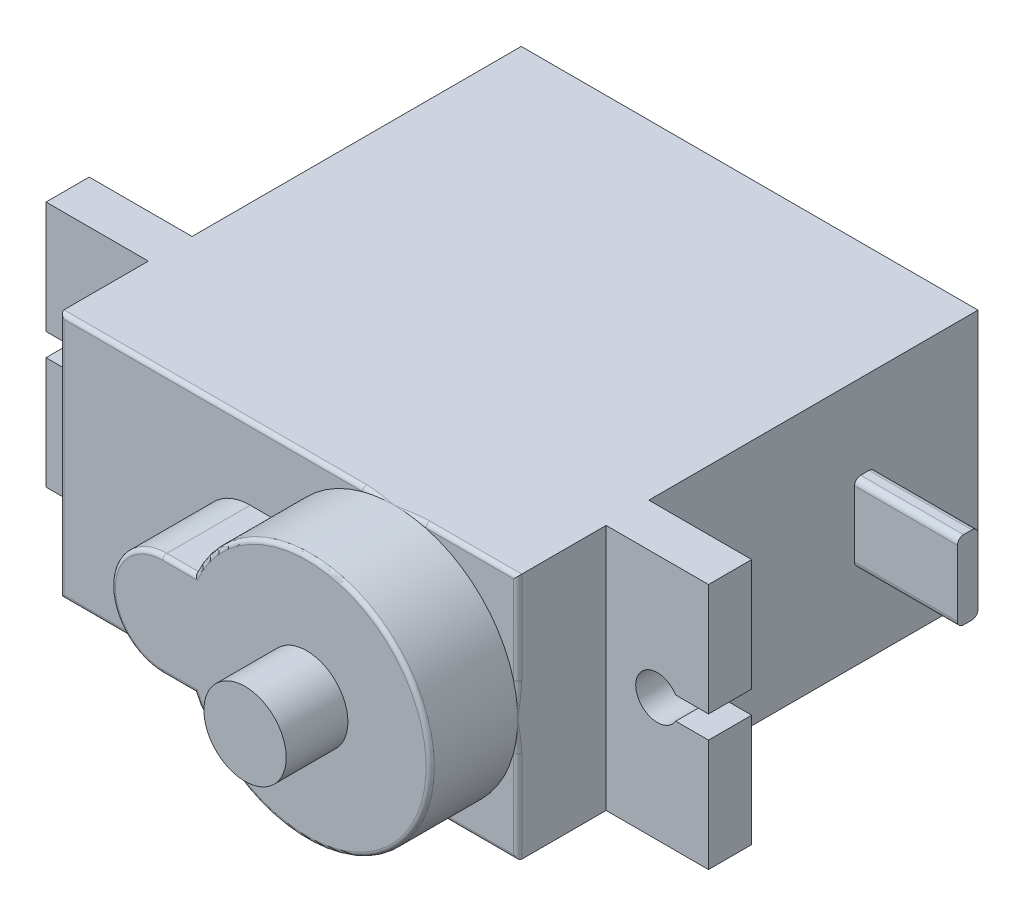
SolidWorks part; units mm, degrees
ref_plane "Ebene vorne" through (0, 0, 0) normal (0, 0, 1) x (1, 0, 0)
ref_plane "Ebene oben" through (0, 0, 0) normal (0, 1, 0) x (1, 0, 0)
ref_plane "Ebene rechts" through (0, 0, 0) normal (1, 0, 0) x (0, 0, -1)
sketch "BasisSkizze" plane through (0, 0, 0) normal (0, 0, 1) x (1, 0, 0)
  line L1 (-16.1, 6) -> (16.1, 6)
  line L2 (-16.1, 6) -> (-16.1, -6)
  line L3 (-16.1, -6) -> (16.1, -6)
  line L4 (16.1, 6) -> (16.1, -6)
  line L5 (-16.1, 6) -> (16.1, -6) construction
  line L6 (-16.1, -6) -> (16.1, 6) construction
  point P0 (0, 0)
  dimension "D1" = 32.2
  dimension "D2" = 12
extrude "Basis" add sketch "BasisSkizze" along normal mid plane 2.1
sketch "Skizze2" plane through (0, 0, 1.05) normal (0, 0, 1) x (1, 0, 0)
  line L0 (-16.1, -6) -> (16.1, -6) construction
  line L1 (-11.125, 6) -> (11.125, 6)
  line L2 (-11.125, 6) -> (-11.125, -6)
  line L3 (-11.125, -6) -> (11.125, -6)
  line L4 (11.125, 6) -> (11.125, -6)
  line L5 (-11.125, 6) -> (11.125, -6) construction
  line L6 (-11.125, -6) -> (11.125, 6) construction
  point P0 (0, 0)
  dimension "D1" = 22.25
extrude "Body oben" add sketch "Skizze2" along normal blind 4.3
sketch "Getriebe" plane through (0, 0, 5.35) normal (0, 0, 1) x (1, 0, 0)
  line L0 (-11.125, 0) -> (11.125, 0) construction
  line L1 (-11.125, 6) -> (-11.125, -6) construction
  line L2 (11.125, -6) -> (11.125, 6) construction
  line L3 (-1.875, 2.5) -> (-0.3294, 2.5)
  line L4 (-1.875, -2.5) -> (-0.3294, -2.5)
  circle A0 centre (5.125, 0) radius 6
  circle A1 centre (-1.875, 0) radius 2.5 construction
  arc A2 (-1.875, 2.5) -> (-1.875, -2.5) centre (-1.875, 0) ccw
  dimension "D1" = 6
  dimension "D2" = 12
  dimension "D3" = 5
  dimension "D4" = 7
extrude "Getriebeaufsatz" add sketch "Getriebe" along normal blind 4.25 contours L3 A2 L4 A0 | A0 region at (-2.3129, 0, 5.35) region at (5.125, 0, 5.35)
fillet "Verrundung1" radius 0.2 7 edges at (8.125, 6, 5.35) (11.125, 3, 5.35) (8.125, -6, 5.35) (-3, 6, 5.35) (11.125, -3, 5.35) (-3, -6, 5.35) (-11.125, 0, 5.35)
fillet "Verrundung2" radius 0.2 4 edges at (-1.1022, 2.5, 9.6) (11.125, 0, 9.6) (-1.1022, -2.5, 9.6) (-4.375, 0, 9.6)
sketch "Skizze5" plane through (0, 0, 9.6) normal (0, 0, 1) x (1, 0, 0)
  line L0 (5.125, 5.8) -> (5.125, -5.8) construction
  line L1 (-4.175, 0) -> (10.925, 0) construction
  arc A0 (-0.1995, -2.3) -> (-0.1995, 2.3) centre (5.125, 0) ccw construction
  arc A1 (-1.875, 2.3) -> (-1.875, -2.3) centre (-1.875, 0) ccw construction
  circle A2 centre (5.125, 0) radius 2
  dimension "D1" = 4
extrude "Stutzen" add sketch "Skizze5" along normal blind 3
sketch "Skizze6" plane through (0, 0, -1.05) normal (0, 0, -1) x (-1, 0, 0)
  line L0 (16.1, -6) -> (-16.1, -6) construction
  line L1 (-11.1, 6) -> (11.1, 6)
  line L2 (-11.1, 6) -> (-11.1, -6)
  line L3 (-11.1, -6) -> (11.1, -6)
  line L4 (11.1, 6) -> (11.1, -6)
  line L5 (-11.1, 6) -> (11.1, -6) construction
  line L6 (-11.1, -6) -> (11.1, 6) construction
  point P0 (0, 0)
  dimension "D1" = 22.2
extrude "Body unten" add sketch "Skizze6" along normal blind 16
sketch "Skizze7" plane through (11.1, 0, 0) normal (1, 0, 0) x (0, 0, -1)
  line L0 (17.05, 0) -> (-12.3825, 0) construction
  line L1 (11.05, -1.9) -> (12.05, -1.9)
  line L2 (11.05, -1.9) -> (11.05, 1.9)
  line L3 (11.05, 1.9) -> (12.05, 1.9)
  line L4 (12.05, -1.9) -> (12.05, 1.9)
  line L5 (11.05, -1.9) -> (12.05, 1.9) construction
  line L6 (11.05, 1.9) -> (12.05, -1.9) construction
  line L7 (17.05, 6) -> (17.05, -6) construction
  point P0 (11.55, 0)
  dimension "D1" = 1
  dimension "D2" = 3.8
  dimension "D3" = 5.5
extrude "Aufsatz-Linear austragen6" add sketch "Skizze7" along normal blind 5
fillet "Verrundung3" radius 0.3 4 edges at (13.6, 1.9, -11.05) (13.6, 1.9, -12.05) (13.6, -1.9, -12.05) (13.6, -1.9, -11.05)
sketch "Schraubenhalterungsskizze" plane through (0, 0, 1.05) normal (0, 0, 1) x (1, 0, 0)
  line L0 (-11.125, 0) -> (-16.1, 0) construction
  line L1 (-11.125, 6) -> (-11.125, -6) construction
  line L2 (-16.1, 6) -> (-16.1, -6) construction
  line L3 (-13.6125, 6) -> (-13.6125, -6) construction
  line L4 (-11.125, 6) -> (-16.1, 6) construction
  line L5 (-16.1, -6) -> (-11.125, -6) construction
  line L7 (-13.225, 0.55) -> (-16.1, 0.55)
  line L8 (-13.225, 0.55) -> (-13.225, -0.55)
  line L9 (-13.225, -0.55) -> (-16.1, -0.55)
  line L10 (-16.1, 0.55) -> (-16.1, -0.55)
  line L11 (-13.225, 0.55) -> (-16.1, -0.55) construction
  line L12 (-13.225, -0.55) -> (-16.1, 0.55) construction
  circle A0 centre (-13.6125, 0) radius 1.05
  point P14 (-14.6625, 0)
  dimension "D1" = 2.1
  dimension "D2" = 1.1
extrude "Halter1" cut sketch "Schraubenhalterungsskizze" against normal blind 10 contours A0 | L10 L9 L8 L7
sketch "Schraubenhalterungsbohrung2" plane through (0, 0, 1.05) normal (0, 0, 1) x (1, 0, 0)
  line L0 (13.6125, 6) -> (13.6125, -6) construction
  line L1 (16.1, 6) -> (11.125, 6) construction
  line L2 (11.125, -6) -> (16.1, -6) construction
  line L3 (11.125, 0) -> (16.1, 0) construction
  line L4 (11.125, -6) -> (11.125, 6) construction
  line L5 (16.1, -6) -> (16.1, 6) construction
  line L7 (13.5744, 0.55) -> (16.1, 0.55)
  line L8 (13.5744, 0.55) -> (13.5744, -0.55)
  line L9 (13.5744, -0.55) -> (16.1, -0.55)
  line L10 (16.1, 0.55) -> (16.1, -0.55)
  line L11 (13.5744, 0.55) -> (16.1, -0.55) construction
  line L12 (13.5744, -0.55) -> (16.1, 0.55) construction
  circle A0 centre (13.6125, 0) radius 1.05
  point P14 (14.8372, 0)
  line M3 (16.1, -6) -> (16.1, 6)
  dimension "D1" = 2.1
  dimension "D2" = 1.1
extrude "Halter2" cut sketch "Schraubenhalterungsbohrung2" against normal blind 10 contours L7 A0 L9 L8 | L9 A0 L7 L8 | A0 L9 L7 M3 region at (13.3756, 0, 1.05) region at (14.0944, 0, 1.05) region at (15.3554, 0, 1.05)
ref_axis "ServoDrehAchse" through (5.125, 0, 12.6) along (0, 0, -1)
